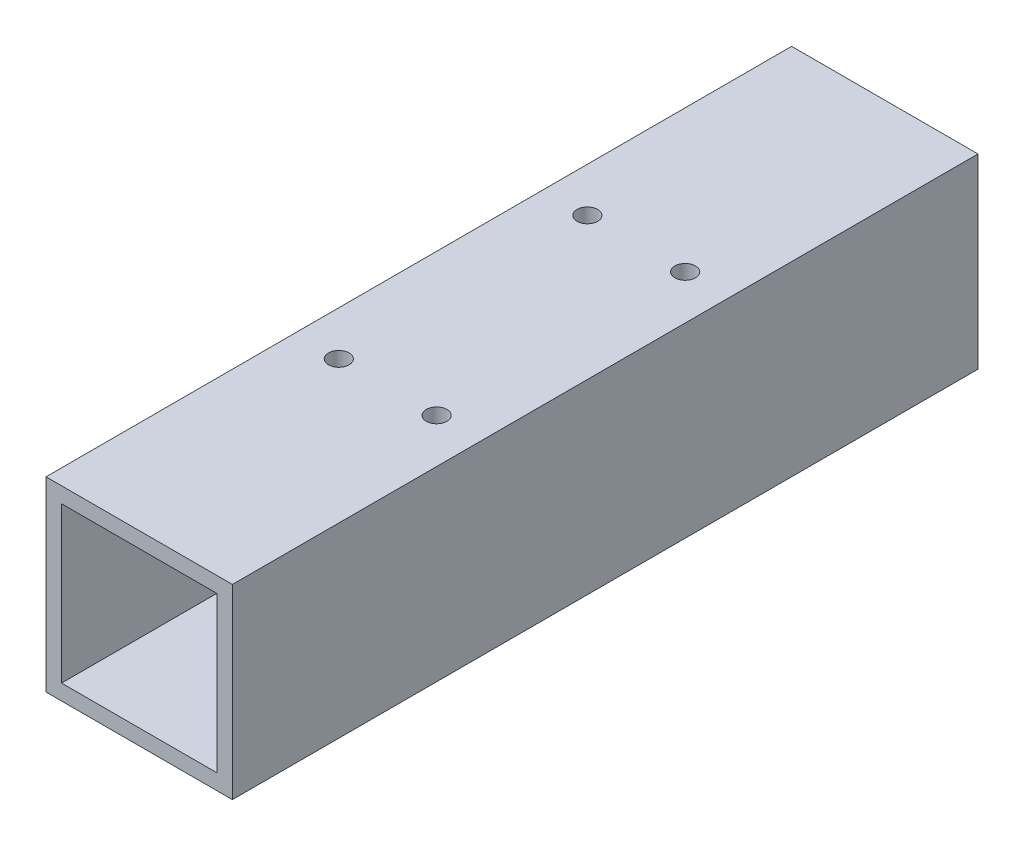
SolidWorks part; units mm, degrees
ref_plane "Front Plane" through (0, 0, 0) normal (0, 0, 1) x (1, 0, 0)
ref_plane "Top Plane" through (0, 0, 0) normal (0, 1, 0) x (1, 0, 0)
ref_plane "Right Plane" through (0, 0, 0) normal (1, 0, 0) x (0, 0, -1)
sketch "Sketch1" plane through (0, 0, 0) normal (0, 0, 1) x (1, 0, 0)
  line L0 (-31.75, 31.75) -> (31.75, 31.75)
  line L2 (-38.1, 38.1) -> (38.1, 38.1)
  line L3 (-38.1, 38.1) -> (-38.1, -38.1)
  line L4 (-38.1, -38.1) -> (38.1, -38.1)
  line L5 (38.1, 38.1) -> (38.1, -38.1)
  line L10 (31.75, 31.75) -> (31.75, -31.75)
  line L11 (-31.75, -31.75) -> (31.75, -31.75)
  line L12 (-31.75, 31.75) -> (-31.75, -31.75)
  point P12 (0, 38.1)
  point P14 (38.1, 0)
  dimension "Wall Thickness" = 6.35
  dimension "Outside Width" = 76.2
  dimension "Outside Height" = 76.2
  dimension "Inside Height" = 63.5
  dimension "Inside Width" = 63.5
sketch "Sketch2" plane through (0, 0, 0) normal (1, 0, 0) x (0, 0, -1)
  line L0 (152.4, 0) -> (-152.4, 0)
  point P4 (0, 0)
  point P7 (-152.4, 0)
  point P10 (152.4, 0)
  dimension "Length" = 304.8
sketch "Sketch3" plane through (0, 0, 0) normal (0, 0, 1) x (1, 0, 0)
  line L21 (38.1, 38.1) -> (-38.1, 38.1)
  line L22 (38.1, -38.1) -> (38.1, 38.1)
  line L23 (-38.1, -38.1) -> (38.1, -38.1)
  line L24 (-38.1, 38.1) -> (-38.1, -38.1)
  line L25 (38.1, 38.1) -> (-38.1, 38.1)
  line L26 (38.1, -38.1) -> (38.1, 38.1)
  line L27 (-38.1, -38.1) -> (38.1, -38.1)
  line L28 (-38.1, 38.1) -> (-38.1, -38.1)
  line L29 (31.75, 31.75) -> (-31.75, 31.75)
  line L30 (31.75, -31.75) -> (31.75, 31.75)
  line L31 (-31.75, -31.75) -> (31.75, -31.75)
  line L32 (-31.75, 31.75) -> (-31.75, -31.75)
  line L33 (31.75, 31.75) -> (-31.75, 31.75)
  line L34 (31.75, -31.75) -> (31.75, 31.75)
  line L35 (-31.75, -31.75) -> (31.75, -31.75)
  line L36 (-31.75, 31.75) -> (-31.75, -31.75)
  dimension "D1" = 0
  dimension "D2" = 0
extrude "Boss-Extrude1" add sketch "Sketch3" along normal up to vertex (152.4 mm away) and the other way up to vertex (152.4 mm away) up to point (0, 0, 152.4) other way up to point (0, 0, -152.4)
sketch "Drawing Reference" plane through (0, 0, 0) normal (1, 0, 0) x (0, 0, -1)
  line L0 (-152.4, 0) -> (152.4, 0) construction
  line L1 (0, -38.1) -> (0, 38.1) construction
  line L2 (-152.4, -38.1) -> (152.4, -38.1) construction
  line L5 (-152.4, 38.1) -> (152.4, 38.1) construction
  point P7 (-129.54, 0)
  point P8 (129.54, 0)
  dimension "D1" = 22.86
hole_wizard "5/16 Clearance Hole3" positions "Sketch12" profile "Sketch13" hole size "5/16" standard "ANSI Inch" end condition through all
sketch "Sketch12" plane through (0, -38.1, 0) normal (0, -1, 0) x (-1, 0, 0)
  line L1 (-20, -50.8) -> (20, -50.8)
  line L2 (-20, -50.8) -> (-20, 50.8)
  line L3 (-20, 50.8) -> (20, 50.8)
  line L4 (20, -50.8) -> (20, 50.8)
  line L5 (-20, -50.8) -> (20, 50.8) construction
  line L6 (-20, 50.8) -> (20, -50.8) construction
  point P2 (20, 50.8)
  point P127 (-20, -50.8)
  point P128 (-20, 50.8)
  point P129 (20, -50.8)
  point P143 (0, 0)
  dimension "D1" = 101.6
  dimension "D2" = 40
sketch "Sketch13" plane through (-20, -38.1, -50.8) normal (1, 0, 0) x (0, 0, -1)
  line L0 (0, 0) -> (0, 76.2)
  line L1 (0, 76.2) -> (4.2164, 76.2)
  line L2 (4.2164, 76.2) -> (4.2164, 0)
  line L5 (4.2164, 0) -> (0, 0)
  line L11 (0, -6.35) -> (0, 107.95) construction
  dimension "Thru Hole Dia." = 8.4328
  dimension "Thru Hole Depth" = 76.2
hole_wizard "1/2 Clearance Hole1" positions "Sketch14" profile "Sketch15" hole size "1/2" standard "ANSI Inch"
sketch "Sketch14" plane through (0, -38.1, 0) normal (0, -1, 0) x (-1, 0, 0)
  point P0 (-20, 50.8)
  point P3 (20, 50.8)
  point P6 (-20, -50.8)
  point P9 (20, -50.8)
sketch "Sketch15" plane through (20, -38.1, -50.8) normal (1, 0, 0) x (0, 0, -1)
  line L0 (0, 0) -> (0, 10.4035)
  line L1 (0, 10.4035) -> (6.7462, 6.35)
  line L2 (6.7462, 6.35) -> (6.7462, 0)
  line L5 (6.7462, 0) -> (0, 0)
  line L10 (0, 10.4035) -> (-6.7462, 6.35) construction
  line L11 (0, -6.35) -> (0, 107.95) construction
  dimension "Hole Dia." = 13.4925
  dimension "Hole Depth" = 6.35
  dimension "Drill Angle" = 118
sketch "Sketch16" plane through (0, -38.1, 0) normal (0, -1, 0) x (1, 0, 0)
  line L0 (0, -152.4) -> (0, 152.4) construction
  line L1 (-38.1, -152.4) -> (38.1, -152.4) construction
  line L2 (-38.1, 152.4) -> (38.1, 152.4) construction
  line L4 (38.1, 152.4) -> (38.1, -152.4) construction
  line L5 (38.1, 0) -> (-38.1, 0) construction
  line L6 (-38.1, 152.4) -> (-38.1, -152.4) construction
  point P12 (0, 0)
equation "\"D1@Drawing Reference\"=\"Outside Width@Sketch1\" * .3"
